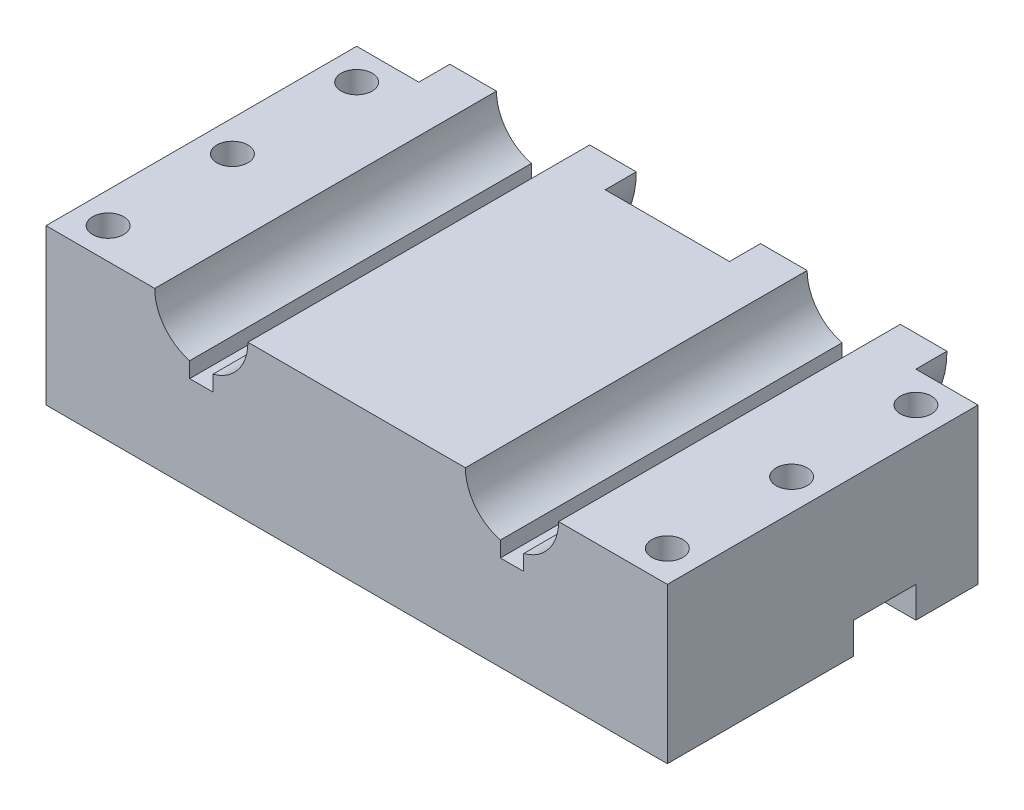
SolidWorks part; units mm, degrees
ref_plane "Front Plane" through (0, 0, 0) normal (0, 0, 1) x (1, 0, 0)
ref_plane "Top Plane" through (0, 0, 0) normal (0, 1, 0) x (1, 0, 0)
ref_plane "Right Plane" through (0, 0, 0) normal (1, 0, 0) x (0, 0, -1)
sketch "Sketch1" plane through (0, 0, 0) normal (0, 1, 0) x (1, 0, 0)
  line L1 (0, 0) -> (254, 0)
  line L2 (0, 0) -> (0, -127)
  line L3 (0, -127) -> (254, -127)
  line L4 (254, 0) -> (254, -127)
  circle A0 centre (12.7, -12.7) radius 6.35
  circle A1 centre (241.3, -12.7) radius 6.35
  circle A2 centre (241.3, -63.5) radius 6.35
  circle A3 centre (241.3, -114.3) radius 6.35
  circle A4 centre (12.7, -63.5) radius 6.35
  circle A5 centre (12.7, -114.3) radius 6.35
  dimension "D3" = 12.7
  dimension "D1" = 254
  dimension "D2" = 127
  dimension "D6" = 50.8
  dimension "D7" = 228.6
  dimension "D8" = 12.7
  dimension "D9" = 12.7
  dimension "D4" = 2
  dimension "D5" = 3
extrude "Boss-Extrude3" add sketch "Sketch1" along normal blind 63.5 contours A4 | A0 | A1 | A2 | A3 | L2 L3 L4 L1 | A5 region at (12.7, 0, 12.7) region at (241.3, 0, 12.7) region at (241.3, 0, 63.5) region at (241.3, 0, 114.3) region at (12.7, 0, 63.5)
sketch "Sketch2" plane through (254, 0, 0) normal (1, 0, 0) x (0, 0, -1)
  line L0 (-25.4, 0) -> (-25.4, 12.7)
  line L1 (0, 0) -> (-127, 0) construction
  line L2 (-25.4, 12.7) -> (-50.8, 12.7)
  line L3 (-50.8, 12.7) -> (-50.8, 0)
  line L4 (0, 63.5) -> (0, 0) construction
  dimension "D1" = 25.4
  dimension "D2" = 25.4
  dimension "D3" = 12.7
extrude "Cut-Extrude1" cut sketch "Sketch2" against normal through all
sketch "Sketch3" plane through (0, 0, 0) normal (0, 0, -1) x (-1, 0, 0)
  line L0 (0, 63.5) -> (-254, 63.5) construction
  line L1 (0, 63.5) -> (0, 0) construction
  line L2 (-127, 0) -> (-127, 63.5) construction
  line L3 (0, 0) -> (-254, 0) construction
  line L4 (-58.7375, 45.0549) -> (-58.7375, 38.7049)
  line L5 (-58.7375, 38.7049) -> (-68.2625, 38.7049)
  line L6 (-68.2625, 38.7049) -> (-68.2625, 45.0549)
  line L7 (-185.7375, 38.7049) -> (-185.7375, 45.0549)
  line L8 (-195.2625, 45.0549) -> (-195.2625, 38.7049)
  line L9 (-195.2625, 38.7049) -> (-185.7375, 38.7049)
  line L10 (-44.45, 63.5) -> (-82.55, 63.5)
  line L11 (-171.45, 63.5) -> (-209.55, 63.5)
  arc A0 (-25.4, 63.5) -> (-101.6, 63.5) centre (-63.5, 63.5) cw
  arc A1 (-44.45, 63.5) -> (-82.55, 63.5) centre (-63.5, 63.5) cw
  arc A2 (-209.55, 63.5) -> (-171.45, 63.5) centre (-190.5, 63.5) ccw
  arc A3 (-228.6, 63.5) -> (-152.4, 63.5) centre (-190.5, 63.5) ccw
  point P15 (-63.5, 38.7049)
  line M7 (0, 63.5) -> (-254, 63.5)
  dimension "D1" = 38.1
  dimension "D2" = 19.05
  dimension "D3" = 63.5
  dimension "D4" = 9.525
  dimension "D5" = 6.35
extrude "Boss-Extrude4" add sketch "Sketch3" along normal blind 12.7 contours A1 L4 L5 L6 A0 M7 | A3 A2 L7 L9 L8 M7 region at (47.7661, 51.3126, 0) region at (190.5, 26.2519, 0)
extrude "Cut-Extrude4" cut sketch "Sketch3<5>" against normal through all contours L4 A1 L6 L5 | A2 M7 | A2 L8 L9 L7 | L10 A1 region at (63.5, 41.6804, 0) region at (190.5, 55.4149, 0) region at (190.5, 41.6804, 0)
sketch "Sketch3<5>" plane through (0, 0, 0) normal (0, 0, -1) x (-1, 0, 0) same geometry as "Sketch3"
